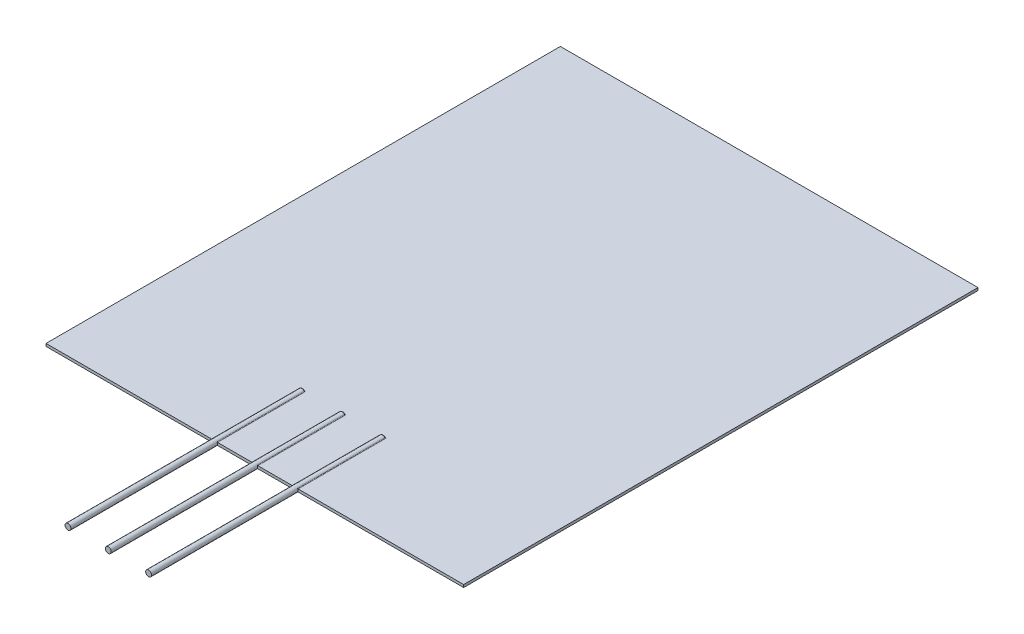
SolidWorks part; units mm, degrees
material "Epoxy, Unfilled"
ref_plane "Front Plane" through (0, 0, 0) normal (0, 0, 1) x (1, 0, 0)
ref_plane "Top Plane" through (0, 0, 0) normal (0, 1, 0) x (1, 0, 0)
ref_plane "Right Plane" through (0, 0, 0) normal (1, 0, 0) x (0, 0, -1)
sketch "Sketch1" plane through (0, 0, 0) normal (0, 1, 0) x (1, 0, 0)
  line L1 (0, 0) -> (28.5, 0)
  line L2 (0, 0) -> (0, 35.1)
  line L3 (0, 35.1) -> (28.5, 35.1)
  line L4 (28.5, 0) -> (28.5, 35.1)
extrude "Boss-Extrude1" add sketch "Sketch1" along normal blind 0.18
sketch "Sketch2" plane through (0, 0, 0) normal (0, 0, 1) x (1, 0, 0)
  circle A0 centre (14.25, 0.09) radius 0.2
  circle A1 centre (17, 0.09) radius 0.2
  circle A2 centre (11.5, 0.09) radius 0.2
extrude "Boss-Extrude2" add sketch "Sketch2" along normal blind 10 and the other way blind 6
fillet "Fillet1" radius 0.05 24 edges at (11.3214, 0, -3) (11.6786, 0, -3) (14.0714, 0, -3) (14.4286, 0, -3) (16.8214, 0, -3) (17.1786, 0, -3) (11.6786, 0.18, -3) (11.3214, 0.18, -3) (17.1786, 0.18, -3) (16.8214, 0.18, -3) (14.4286, 0.18, -3) (14.0714, 0.18, -3) (11.5, -0.11, -6) (11.5, 0, -6) (14.25, -0.11, -6) (14.25, 0, -6) (17, -0.11, -6) (17, 0, -6) (11.5, 0.18, -6) (11.5, 0.29, -6) (17, 0.18, -6) (17, 0.29, -6) (14.25, 0.18, -6) (14.25, 0.29, -6)
